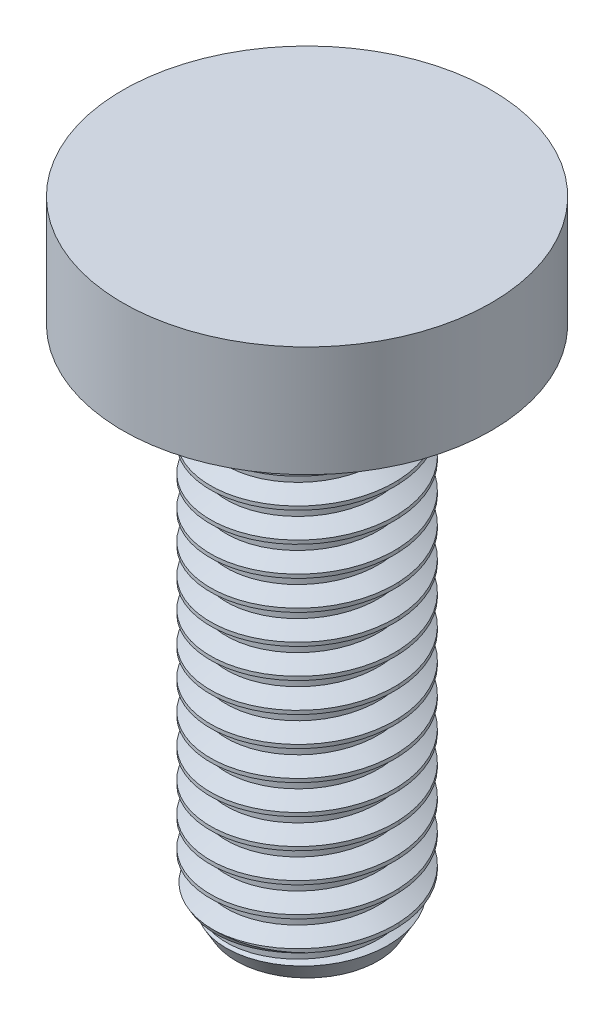
SolidWorks part; units mm, degrees
material "Акрил (Средняя-высокая ударопрочность)"
ref_plane "Спереди" through (0, 0, 0) normal (0, 0, 1) x (1, 0, 0)
ref_plane "Сверху" through (0, 0, 0) normal (0, 1, 0) x (1, 0, 0)
ref_plane "Справа" through (0, 0, 0) normal (1, 0, 0) x (0, 0, -1)
sketch "Эскиз1" plane through (0, 0, 0) normal (0, 0, 1) x (1, 0, 0)
  line L0 (0, 3) -> (-5, 3)
  line L1 (-5, 3) -> (-5, 0)
  line L2 (-5, 0) -> (-2.5, 0)
  line L3 (-2.5, 0) -> (-2.5, -14)
  line L4 (-2.5, -14) -> (0, -14)
  line L5 (0, -14) -> (0, 3)
  dimension "D1" = 5
  dimension "D2" = 3
  dimension "D3" = 2.5
  dimension "D4" = 14
revolve "Повернуть1" add sketch "Эскиз1" angle 360 about L5
chamfer "Фаска1" distance 1 angle 30 1 edges at (2.5, -14, 0)
thread "Резьба1" pitch 0.8 start angle 0, offset 2, length 0, pitch 0.8, diameter 5
ref_plane "Плоскость2" through (2.5, -16, 0) normal (0, 0, 1) x (1, 0, 0)
sketch "Профиль резьбы2" plane through (2.5, -16, 0) normal (0, 0, 1) x (1, 0, 0)
  line L0 (0, 0) -> (0, 0.8) construction
  line L11 (0, 0) -> (0, 0.7)
  line L12 (0, 0.7) -> (-0.433, 0.45)
  line L13 (-0.433, 0.45) -> (-0.433, 0.25)
  line L15 (-0.433, 0.25) -> (0, 0)
  line L17 (-0.433, 0.35) -> (0, 0.35) construction
  point P2 (0, 0)
  dimension "Pitch" = 0.8
  dimension "Profile_Angle" = 60
  dimension "Profile_Land" = 0.2
  dimension "Profile_Height" = 0.433
